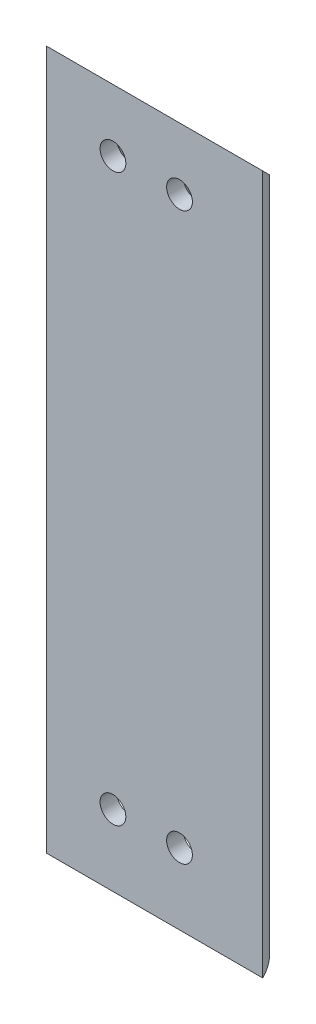
SolidWorks part; units mm, degrees
ref_plane "Front Plane" through (0, 0, 0) normal (0, 0, 1) x (1, 0, 0)
ref_plane "Top Plane" through (0, 0, 0) normal (0, 1, 0) x (1, 0, 0)
ref_plane "Right Plane" through (0, 0, 0) normal (1, 0, 0) x (0, 0, -1)
sketch "Sketch1" plane through (0, 0, 0) normal (0, 1, 0) x (1, 0, 0)
  line L0 (0, 28.575) -> (0, 0)
  line L1 (0, 0) -> (41.275, 0)
  line L2 (41.275, 0) -> (41.275, 3.175)
  line L3 (41.275, 3.175) -> (3.175, 3.175)
  line L4 (3.175, 3.175) -> (3.175, 28.575)
  line L5 (3.175, 28.575) -> (0, 28.575)
  dimension "D1" = 25.4
  dimension "D2" = 38.1
  dimension "D3" = 3.175
  dimension "D4" = 3.175
extrude "Boss-Extrude1" add sketch "Sketch1" along normal mid plane 133.35
fillet "Fillet1" radius 3.175 2 edges at (41.275, 0, -3.175) (3.175, 0, -28.575)
sketch "Sketch4" plane through (0, 0, 0) normal (-1, 0, 0) x (0, 0, 1)
  line L0 (0, -66.675) -> (-28.575, -38.1)
  line L1 (-28.575, 66.675) -> (-28.575, -66.675) construction
  line L2 (0, 66.675) -> (0, -66.675) construction
  line L3 (0, 66.675) -> (-28.575, 38.1)
  line L4 (-28.575, -38.1) -> (-28.575, -66.675)
  line L5 (-28.575, -66.675) -> (0, -66.675)
  line L6 (-28.575, 66.675) -> (0, 66.675)
  line L7 (-28.575, 66.675) -> (-28.575, 38.1)
  dimension "D1" = 45
  dimension "D2" = 45
extrude "Cut-Extrude1" cut sketch "Sketch4" against normal through all
hole_wizard "#10 (0.1935) Diameter Hole1" positions "Sketch8" profile "Sketch7" hole size "#10" standard "ANSI Inch" end condition through all
sketch "Sketch8" plane through (0, 0, -3.175) normal (0, 0, -1) x (-1, 0, 0)
  line L2 (0, 66.675) -> (0, -66.675) construction
  point P0 (-25.4, -53.0928)
  point P15 (-12.7, -53.0928)
  point P16 (-12.7, 54.8572)
  point P17 (-25.4, 54.8572)
  dimension "D1" = 12.7
  dimension "D2" = 2
  dimension "D3" = 2
sketch "Sketch7" plane through (25.4, -53.0928, -3.175) normal (1, 0, 0) x (0, 1, 0)
  line L0 (0, 0) -> (0, 3.175)
  line L1 (0, 3.175) -> (2.4574, 3.175)
  line L2 (2.4574, 3.175) -> (2.4574, 0)
  line L5 (2.4574, 0) -> (0, 0)
  line L11 (0, -6.35) -> (0, 107.95) construction
  dimension "Thru Hole Dia." = 4.9149
  dimension "Thru Hole Depth" = 3.175
